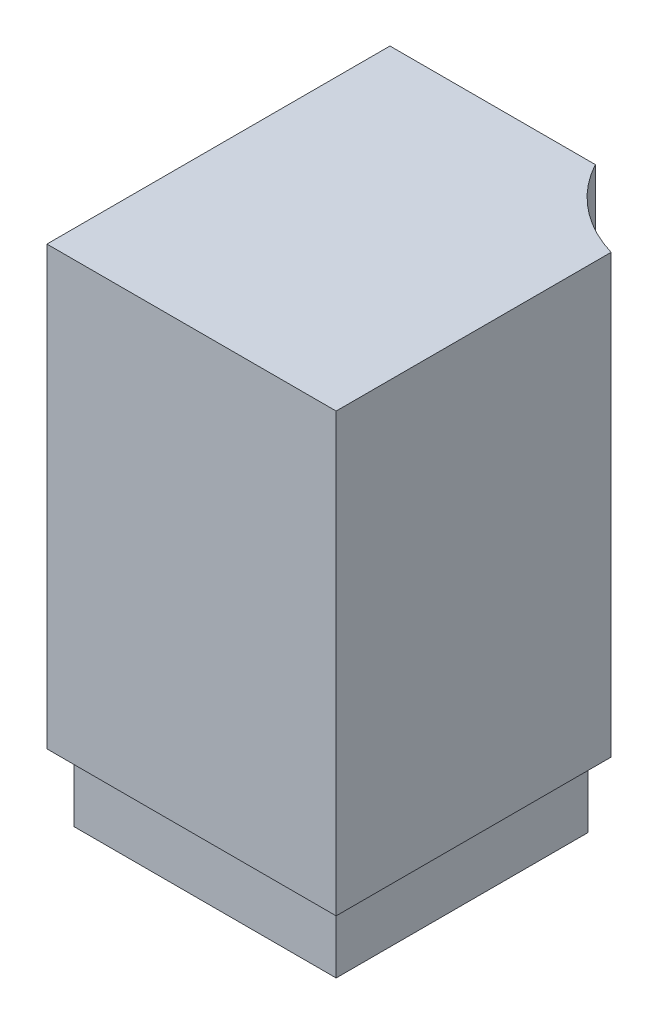
SolidWorks part; units mm, degrees
ref_plane "正面" through (0, 0, 0) normal (0, 0, 1) x (1, 0, 0)
ref_plane "平面" through (0, 0, 0) normal (0, 1, 0) x (1, 0, 0)
ref_plane "右側面" through (0, 0, 0) normal (1, 0, 0) x (0, 0, -1)
sketch "ｽｹｯﾁ1" plane through (0, 0, 0) normal (0, 1, 0) x (1, 0, 0)
  line L1 (0, 0) -> (39, 0)
  line L2 (0, 0) -> (0, -47)
  line L3 (0, -47) -> (39, -47)
  line L4 (39, 0) -> (39, -47)
  circle A0 centre (47, 12) radius 23
  dimension "D5" = 46
  dimension "D1" = 47
  dimension "D2" = 39
  dimension "D3" = 47
  dimension "D4" = 12
extrude "ﾎﾞｽ - 押し出し1" add sketch "ｽｹｯﾁ1" against normal blind 10 contours A0 L1 L2 L3 L4 region at (18.9111, 0, 24.2723)
ref_plane "平面1" through (19.5, 0, 0) normal (1, 0, 0) x (0, 0, -1)
sketch "ｽｹｯﾁ2" plane through (0, -10, 0) normal (0, -1, 0) x (1, 0, 0)
  line L0 (0, 47) -> (39, 47) construction
  line L1 (13, 37) -> (26, 37)
  line L2 (13, 37) -> (13, 11)
  line L3 (13, 11) -> (26, 11)
  line L4 (26, 37) -> (26, 11)
  line L5 (0, 47) -> (39, 47)
  point P4 (19.5, 37)
  point P7 (19.5, 47)
  dimension "D1" = 26
  dimension "D2" = 13
  dimension "D3" = 10
extrude "ﾎﾞｽ - 押し出し2" add sketch "ｽｹｯﾁ2" along normal blind 10 contours L4 L1 L2 L3 region at (19.5, -10, 24)
sketch "ｽｹｯﾁ3" plane through (0, 0, 0) normal (0, 1, 0) x (1, 0, 0)
  line L4 (0, 0) -> (27.3786, 0) construction
  line L5 (-2, 2) -> (28.5338, 2)
  line L6 (-2, 2) -> (-2, -49)
  line L7 (-2, -49) -> (41, -49)
  line L14 (41, -8.1246) -> (41, -49)
  line L15 (0, 0) -> (0, -47) construction
  line L16 (0, -47) -> (39, -47) construction
  line L17 (39, -9.5639) -> (39, -47) construction
  arc A1 (28.5338, 2) -> (41, -8.1246) centre (47, 12) ccw
  arc A4 (27.3786, 0) -> (39, -9.5639) centre (47, 12) ccw construction
  dimension "D4" = 2
  dimension "D5" = 2
  dimension "D1" = 2
  dimension "D2" = 2
  dimension "D3" = 2
extrude "ﾎﾞｽ - 押し出し3" add sketch "ｽｹｯﾁ3" along normal blind 65 contours A1 L14 L7 L6 L5
